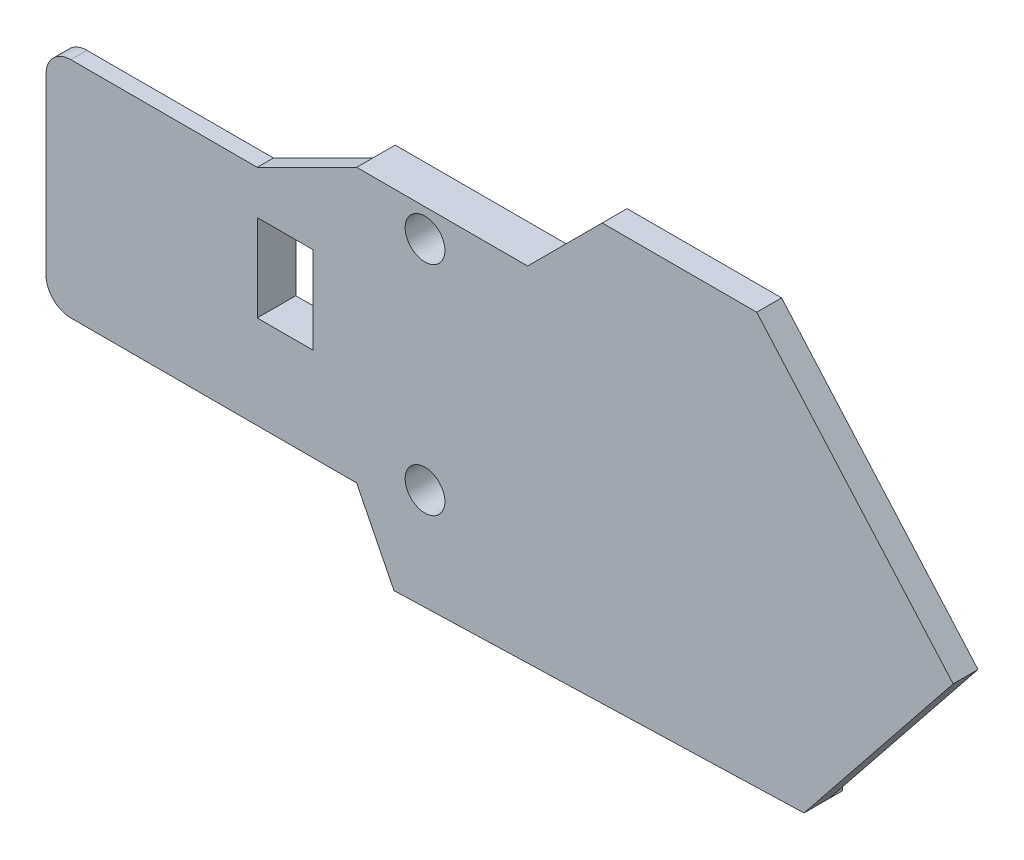
SolidWorks part; units mm, degrees
ref_plane "Front Plane" through (0, 0, 0) normal (0, 0, 1) x (1, 0, 0)
ref_plane "Top Plane" through (0, 0, 0) normal (0, 1, 0) x (1, 0, 0)
ref_plane "Right Plane" through (0, 0, 0) normal (1, 0, 0) x (0, 0, -1)
sketch "Sketch1" plane through (0, 0, 0) normal (0, 0, 1) x (1, 0, 0)
  line L0 (18, -11) -> (18, -16)
  line L1 (-18, -11) -> (18, -11) construction
  line L2 (-18, -11) -> (-18, 11)
  line L3 (-18, 11) -> (18, 11)
  line L4 (18, -11) -> (18, 11)
  line L5 (-18, -11) -> (18, 11) construction
  line L6 (-18, 11) -> (18, -11) construction
  line L7 (18, -16) -> (-15, -17)
  line L8 (-15, -17) -> (-18, -11)
  line L9 (-12.5, 11) -> (-12.5, -11) construction
  line L10 (-12.5, 8.75) -> (-18, 0) construction
  line L11 (-18, 0) -> (-12.5, -8.75) construction
  circle A0 centre (-12.5, 8.75) radius 1.6
  circle A1 centre (-12.5, -8.75) radius 1.6
  point P0 (0, 0)
  dimension "D7" = 3.2
  dimension "D1" = 5
  dimension "D2" = 6
  dimension "D3" = 3
  dimension "D4" = 22
  dimension "D5" = 36
  dimension "D6" = 17.5
  dimension "D8" = 5.5
extrude "Boss-Extrude1" add sketch "Sketch1" along normal blind 1.1
chamfer "Chamfer1" distance 5 angle 45 1 edges at (18, 11, 0.55)
sketch "Sketch2" plane through (0, 0, 1.1) normal (0, 0, 1) x (1, 0, 0)
  line L0 (18, 6) -> (21.5355, 9.5355)
  line L1 (21.5355, 9.5355) -> (15.0711, 16)
  line L2 (15.0711, 16) -> (5, 16)
  line L3 (5, 16) -> (5, 11)
  line L6 (18, -16) -> (18, 6)
  line L7 (18, 6) -> (13, 11)
  line L8 (13, 11) -> (-18, 11)
  line L9 (-18, 11) -> (-18, -11)
  line L10 (-18, -11) -> (-15, -17)
  line L11 (-15, -17) -> (18, -16)
  line L12 (18, -16) -> (18, 6)
  line L13 (18, 6) -> (13, 11)
  line L14 (13, 11) -> (-18, 11)
  line L15 (-18, 11) -> (-18, -11)
  line L16 (-18, -11) -> (-15, -17)
  line L17 (-15, -17) -> (18, -16)
  circle A0 centre (-12.5, 8.75) radius 1.6 construction
  circle A1 centre (-12.5, 8.75) radius 1.6
  circle A2 centre (-12.5, -8.75) radius 1.6 construction
  circle A3 centre (-12.5, -8.75) radius 1.6
  line M10 (18, -16) -> (18, 6)
  line M11 (18, 6) -> (13, 11)
  line M12 (13, 11) -> (-18, 11)
  line M13 (-18, 11) -> (-18, -11)
  line M14 (-18, -11) -> (-15, -17)
  line M15 (-15, -17) -> (18, -16)
  circle M16 centre (-12.5, 8.75) radius 1.6
  circle M17 centre (-12.5, -8.75) radius 1.6
  dimension "D2" = 5
  dimension "D3" = 5
  dimension "D4" = 8
  dimension "D1" = 0
extrude "Boss-Extrude2" add sketch "Sketch2" along normal blind 2 contours M15 M10 M11 M12 M13 M14 M16 M17 | L2 L3 L0 L1 M12 M11 region at (13.0483, 12.2379, 1.1) region at (0.0361, -2.8626, 1.1)
chamfer "Chamfer2" distance 5 angle 45 1 edges at (5, 11, 2.1)
sketch "Sketch3" plane through (0, 0, 1.1) normal (0, 0, -1) x (-1, 0, 0)
  line L0 (-18, -16) -> (-30, -1)
  line L1 (-30, -1) -> (-15.0711, 16)
  line L2 (-15.0711, 16) -> (-18, 6)
  line L3 (-18, 6) -> (-18, -16)
  line L4 (-15.0711, 16) -> (-14.1929, 17)
  line L5 (-14.1929, 17) -> (-1.7574, 17)
  line L6 (-1.7574, 17) -> (4.2426, 11)
  line L7 (-13, 11) -> (18, 11) construction
  line L8 (4.2426, 11) -> (-13, 11)
  line L9 (-13, 11) -> (-15.0711, 16)
  line L10 (-15.0711, 16) -> (-5, 16) construction
  line L11 (0, 11) -> (-5, 16) construction
  point P18 (-29.2022, -0.8225)
  line M10 (-21.5355, 9.5355) -> (-18, 6)
  line M13 (0, 11) -> (-5, 16)
  line M14 (-5, 16) -> (-15.0711, 16)
  dimension "D1" = 1
  dimension "D2" = 3
  dimension "D3" = 12
  dimension "D4" = 15
extrude "Boss-Extrude4" add sketch "Sketch3" against normal blind 2 contours L3 L1 L0 M10 | L8 L6 L5 L4 M14 M13 region at (3.3041, 14.6555, 1.1) region at (22.1903, -2.133, 1.1)
sketch "Sketch4" plane through (0, 0, 1.1) normal (0, 0, -1) x (-1, 0, 0)
  line L0 (-21.1162, 9.1162) -> (-14.1929, 17)
  line L1 (-14.1929, 17) -> (-26.9656, 17)
  line L2 (-26.9656, 17) -> (-24.4968, 9.1162)
  line L3 (-24.4968, 9.1162) -> (-21.1162, 9.1162)
extrude "Cut-Extrude1" cut sketch "Sketch4" against normal through all
sketch "Sketch5" plane through (0, 0, 0) normal (0, 0, -1) x (-1, 0, 0)
  line L0 (18, 11) -> (18, -11) construction
  line L1 (18, 11) -> (18, -11)
  line L2 (18, -11) -> (21, -5)
  line L3 (21, -5) -> (34, -5)
  line L4 (34, -5) -> (34, 5)
  line L5 (34, 5) -> (18, 5)
  line L6 (-13, 11) -> (18, 11) construction
  line L7 (21.5, 3.5) -> (26, 3.5)
  line L8 (21.5, 3.5) -> (21.5, -3.5)
  line L9 (21.5, -3.5) -> (26, -3.5)
  line L10 (26, 3.5) -> (26, -3.5)
  line L11 (18, -11) -> (15, -17) construction
  line M13 (18, -11) -> (18, 11)
  dimension "D1" = 6
  dimension "D2" = 6
  dimension "D3" = 7
  dimension "D4" = 3.5
  dimension "D5" = 4.5
  dimension "D6" = 16
  dimension "D7" = 7.5
extrude "Boss-Extrude5" add sketch "Sketch5" against normal up to surface (3.1 mm away) contours L4 L5 L2 L3 L7 L10 L9 L8 M13 region at (-26.0573, -0.4582, 0) up to face at (1.0885, 1.375, 3.1)
sketch "Sketch6" plane through (0, 0, 3.1) normal (0, 0, 1) x (1, 0, 0)
  line L0 (-18, 11) -> (-26, 7)
  line L1 (-26, 7) -> (-43, 7)
  line L2 (-43, 7) -> (-43, -11)
  line L3 (-43, -11) -> (-18, -11)
  line L5 (-18, 11) -> (-18, -11) construction
  line L6 (-18, -11) -> (-21, -5) construction
  line L7 (-21, -5) -> (-34, -5) construction
  line L8 (-34, -5) -> (-34, 5) construction
  line L9 (-21.5, 3.5) -> (-26, 3.5)
  line L10 (-26, 3.5) -> (-26, -3.5)
  line L11 (-26, -3.5) -> (-21.5, -3.5)
  line L12 (-21.5, -3.5) -> (-21.5, 3.5)
  line L13 (-21.5, 3.5) -> (-26, 3.5)
  line L14 (-26, 3.5) -> (-26, -3.5)
  line L15 (-26, -3.5) -> (-21.5, -3.5)
  line L16 (-21.5, -3.5) -> (-21.5, 3.5)
  line L17 (-34, 5) -> (-18, 5) construction
  line L18 (-18, 11) -> (-18, -11)
  line L19 (-18, -11) -> (-21, -5)
  line L20 (-21, -5) -> (-34, -5)
  line L21 (-34, -5) -> (-34, 5)
  line L22 (-34, 5) -> (-18, 5)
  line L23 (-4.2426, 11) -> (-18, 11) construction
  point P10 (-18.2074, -10.5852)
  line M14 (-18, 11) -> (-18, 5)
  line M15 (-18, 5) -> (-34, 5)
  line M16 (-34, 5) -> (-34, -5)
  line M17 (-34, -5) -> (-21, -5)
  line M18 (-21, -5) -> (-15, -17)
  dimension "D2" = 25
  dimension "D3" = 4
  dimension "D4" = 8
  dimension "D1" = 0
extrude "Boss-Extrude6" add sketch "Sketch6" against normal blind 1.3 contours L2 L3 L0 L1 M18 M17 M16 M15 M14 region at (-18.333, 8, 3.1)
fillet "Fillet1" radius 2 2 edges at (-43, 7, 2.45) (-43, -11, 2.45)
